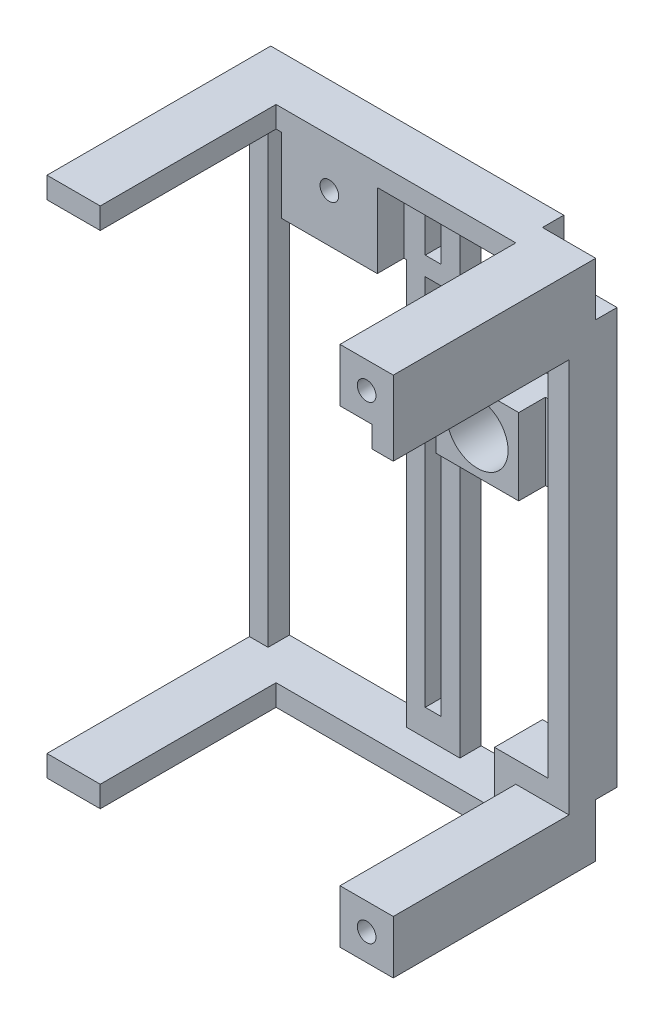
SolidWorks part; units mm, degrees
ref_plane "Front Plane" through (0, 0, 0) normal (0, 0, 1) x (1, 0, 0)
ref_plane "Top Plane" through (0, 0, 0) normal (0, 1, 0) x (1, 0, 0)
ref_plane "Right Plane" through (0, 0, 0) normal (1, 0, 0) x (0, 0, -1)
sketch "Sketch1" plane through (0, 0, 0) normal (0, 0, 1) x (1, 0, 0)
  line L0 (0, 94) -> (65, 94)
  line L1 (0, 0) -> (65, 0)
  line L2 (0, 0) -> (0, 98)
  line L3 (0, 98) -> (65, 98)
  line L4 (65, 0) -> (65, 98)
  line L5 (65, 98) -> (55, 98)
  line L6 (65, 98) -> (65, 88)
  line L7 (65, 88) -> (55, 88)
  line L8 (55, 98) -> (55, 88)
  line L9 (65, 0) -> (55, 0)
  line L10 (65, 0) -> (65, 10)
  line L11 (65, 10) -> (55, 10)
  line L12 (55, 0) -> (55, 10)
  line L13 (0, 4) -> (65, 4)
  line L14 (61, 0) -> (61, 98)
  line L15 (20, 9) -> (33, 9)
  line L16 (65, 98) -> (51, 98)
  line L17 (65, 98) -> (65, 84)
  line L18 (65, 84) -> (51, 84)
  line L19 (51, 98) -> (51, 84)
  line L20 (65, 0) -> (51, 0)
  line L21 (65, 0) -> (65, 14)
  line L22 (65, 14) -> (51, 14)
  line L23 (51, 0) -> (51, 14)
  line L24 (15, 84) -> (25, 84)
  line L25 (15, 84) -> (15, 94)
  line L26 (15, 94) -> (25, 94)
  line L27 (25, 84) -> (25, 94)
  line L28 (15, 84) -> (25, 94) construction
  line L29 (15, 94) -> (25, 84) construction
  line L30 (11, 94) -> (29, 94)
  line L31 (11, 94) -> (11, 80)
  line L32 (11, 80) -> (29, 80)
  line L33 (29, 94) -> (29, 80)
  line L34 (36, 70.6615) -> (39.5, 70.6615)
  line L35 (33, 9) -> (36, 9)
  line L36 (33, 9) -> (33, 79)
  line L37 (33, 79) -> (36, 79)
  line L38 (36, 9) -> (36, 79)
  line L40 (40.05, 70.6855) -> (55.55, 70.6855)
  line L41 (40.05, 70.6855) -> (40.05, 56.3145)
  line L42 (40.05, 56.3145) -> (55.55, 56.3145)
  line L43 (55.55, 70.6855) -> (55.55, 56.3145)
  line L44 (40.05, 70.6855) -> (55.55, 56.3145) construction
  line L45 (40.05, 56.3145) -> (55.55, 70.6855) construction
  circle A0 centre (20, 89) radius 1.75
  circle A1 centre (20, 9) radius 1.75
  circle A2 centre (47.8, 63.5) radius 5.75
  dimension "D9" = 3.5
  dimension "D11" = 3.5
  dimension "D28" = 11.5
  dimension "D1" = 98
  dimension "D2" = 65
  dimension "D3" = 10
  dimension "D4" = 10
  dimension "D5" = 10
  dimension "D6" = 10
  dimension "D7" = 45
  dimension "D8" = 9
  dimension "D10" = 80
  dimension "D12" = 4
  dimension "D13" = 4
  dimension "D14" = 4
  dimension "D15" = 14
  dimension "D16" = 14
  dimension "D17" = 14
  dimension "D18" = 14
  dimension "D19" = 10
  dimension "D20" = 9
  dimension "D21" = 9
  dimension "D22" = 4
  dimension "D23" = 13
  dimension "D24" = 70
  dimension "D25" = 3
  dimension "D26" = 3.5
  dimension "D27" = 13.2
  dimension "D29" = 20.5
  dimension "D30" = 15.5
extrude "Boss-Extrude2" add sketch "Sketch1" along normal blind 5 contours L33 L0 L27 L24 L25 L31 L32 | L19 L3 L2 L0 | L24 L27 L0 L25 A0 | L0 L19 L18 L14 L7 L8 | L3 L19 L0 L8 | L18 L4 L7 L14 | L22 L4 L18 L14 | L14 L7 L4 L0 | L7 L14 L0 L8 | L0 L14 L3 L8 | L14 L0 L4 L5 | L23 L13 L12 L11 L14 L22 | L13 L14 L11 L12 | L14 L13 L10 L11 | L4 L22 L14 L11 | L14 L9 L4 L13 | L1 L14 L13 L12 | L23 L1 L12 L13 | L1 L23 L13 L2 region at (25.5, 96, 0) region at (13, 93.772, 0) region at (25.5, 2, 0) region at (20, 93.8586, 0) region at (54.875, 10.125, 0) region at (53, 2, 0) region at (53, 96, 0) region at (58, 2, 0) region at (58, 7, 0) region at (58, 96, 0) region at (54.875, 87.875, 0) region at (63, 7, 0) region at (63, 2, 0) region at (63, 12, 0) region at (63, 49, 0) region at (63, 96, 0) region at (58, 91, 0) region at (63, 86, 0) region at (63, 91, 0)
extrude "Boss-Extrude4" add sketch "Sketch1<18>" against normal blind 4 contours L0 L33 L32 L31 L2 L13 L23 L22 L14 L18 L19 A1 | L1 L23 L13 L2 | L22 L4 L18 L14 | L0 L19 L18 L14 L7 L8 | L3 L19 L0 L8 | L18 L4 L7 L14 | L19 L3 L2 L0 | L33 L0 L27 L24 L25 L31 L32 | A1 | L23 L13 L12 L11 L14 L22 | L4 L22 L14 L11 | L23 L1 L12 L13 | L41 L40 L43 L42 region at (25.5, 96, 0) region at (28.9667, 46.5257, 0) region at (13, 93.772, 0) region at (25.5, 2, 0) region at (54.875, 10.125, 0) region at (53, 2, 0) region at (53, 96, 0) region at (54.875, 87.875, 0) region at (63, 12, 0) region at (63, 49, 0) region at (63, 86, 0) region at (18.2995, 9, 0)
sketch "Sketch1<18>" plane through (0, 0, 0) normal (0, 0, 1) x (1, 0, 0) same geometry as "Sketch1"
extrude "Boss-Extrude5" add sketch "Sketch1<22>" along normal blind 38 contours L1 L23 L13 L2 | L23 L1 L12 L13 | L1 L14 L13 L12 | L14 L9 L4 L13 | L14 L13 L10 L11 | L4 L22 L14 L11 | L22 L4 L18 L14 | L13 L14 L11 L12 | L18 L4 L7 L14 | L14 L7 L4 L0 | L7 L14 L0 L8 | L14 L0 L4 L5 | L0 L14 L3 L8 | L3 L19 L0 L8 | L19 L3 L2 L0 region at (25.5, 96, 0) region at (25.5, 2, 0) region at (53, 2, 0) region at (53, 96, 0) region at (58, 2, 0) region at (58, 7, 0) region at (58, 96, 0) region at (63, 7, 0) region at (63, 2, 0) region at (63, 12, 0) region at (63, 49, 0) region at (63, 96, 0) region at (58, 91, 0) region at (63, 86, 0) region at (63, 91, 0)
sketch "Sketch1<22>" plane through (0, 0, 0) normal (0, 0, 1) x (1, 0, 0) same geometry as "Sketch1"
sketch "Sketch2" plane through (0, 0, 38) normal (0, 0, 1) x (1, 0, 0)
  line L5 (0, 98) -> (65, 98) construction
  line L10 (65, 0) -> (65, 98) construction
  line L11 (0, 0) -> (65, 0) construction
  circle A0 centre (60, 93) radius 1.75
  circle A1 centre (60, 5) radius 1.75
  dimension "D1" = 3.5
  dimension "D2" = 5
  dimension "D4" = 3.5
  dimension "D3" = 5
  dimension "D5" = 5
  dimension "D6" = 5
extrude "Cut-Extrude1" cut sketch "Sketch2" against normal through all
extrude "Boss-Extrude6" add sketch "Sketch1<23>" along normal blind 5 contours L43 L40 L41 L42 A2
sketch "Sketch1<23>" plane through (0, 0, 0) normal (0, 0, 1) x (1, 0, 0) same geometry as "Sketch1"
extrude "Cut-Extrude4" cut sketch "Sketch1<25>" against normal through all contours A2 region at (47.8, 63.5, 0)
sketch "Sketch1<25>" plane through (0, 0, 0) normal (0, 0, 1) x (1, 0, 0) same geometry as "Sketch1"
sketch "Sketch9" plane through (0, 0, 38) normal (0, 0, 1) x (1, 0, 0)
  line L0 (10, 4) -> (10, 0)
  line L1 (0, 4) -> (51, 4) construction
  line L2 (0, 0) -> (65, 0) construction
  line L3 (0, 0) -> (0, 4) construction
  line L4 (10, 94) -> (10, 98)
  line L5 (0, 94) -> (11, 94) construction
  line L6 (0, 98) -> (65, 98) construction
  line L7 (0, 94) -> (0, 98) construction
  line L8 (65, 0) -> (65, 98) construction
  line L9 (51, 94) -> (10, 94)
  line L10 (51, 94) -> (51, 98)
  line L11 (51, 98) -> (10, 98)
  line L12 (10, 94) -> (10, 98)
  line L13 (51, 4) -> (10, 4)
  line L14 (51, 4) -> (51, 0)
  line L15 (51, 0) -> (10, 0)
  line L16 (10, 4) -> (10, 0)
  line L17 (61, 84) -> (65, 84)
  line L18 (61, 84) -> (61, 14)
  line L19 (61, 14) -> (65, 14)
  line L20 (65, 84) -> (65, 14)
  line L21 (61, 14) -> (51, 14) construction
  line L23 (55, 94) -> (51, 94)
  line L24 (55, 94) -> (55, 98)
  line L25 (55, 98) -> (51, 98)
  line L26 (51, 94) -> (51, 98)
  line L27 (65, 84) -> (61, 84)
  line L28 (65, 84) -> (65, 88)
  line L29 (65, 88) -> (61, 88)
  line L30 (61, 84) -> (61, 88)
  line L31 (65, 14) -> (61, 14)
  line L32 (65, 14) -> (65, 10)
  line L33 (65, 10) -> (61, 10)
  line L34 (61, 14) -> (61, 10)
  line L35 (55, 4) -> (51, 4)
  line L36 (55, 4) -> (55, 0)
  line L37 (55, 0) -> (51, 0)
  line L38 (51, 4) -> (51, 0)
  line M5 (65, 0) -> (65, 98)
  line M6 (65, 98) -> (0, 98)
  line M8 (0, 94) -> (55, 94)
  line M11 (61, 88) -> (61, 10)
  line M14 (55, 4) -> (0, 4)
  line M16 (0, 0) -> (65, 0)
  dimension "D1" = 10
  dimension "D2" = 10
  dimension "D3" = 0
extrude "Cut-Extrude6" cut sketch "Sketch9" against normal blind 33 contours L19 L17 M11 M5 | L10 L4 M8 M6 | L14 L0 M14 M16 | L36 L35 L38 L37 | L32 L31 L34 L33 | L24 L23 L26 L25 region at (30.5, 2, 38) region at (63, 49, 38) region at (30.5, 96, 38)
ref_plane "MirrorPlane" through (0, 98, 38) normal (0, 0, -1) x (-1, 0, 0)
sketch "Sketch10" plane through (0, 0, 0) normal (0, 0, 1) x (1, 0, 0)
  line L0 (0, 4) -> (51, 4) construction
  line L1 (0, 94) -> (3.5, 94)
  line L2 (0, 94) -> (0, 4)
  line L3 (0, 4) -> (3.5, 4)
  line L4 (3.5, 94) -> (3.5, 4)
  line L5 (29, 94) -> (51, 94) construction
  line L6 (33, 94) -> (29.5, 94)
  line L7 (33, 94) -> (33, 4)
  line L8 (33, 4) -> (29.5, 4)
  line L9 (29.5, 94) -> (29.5, 4)
  line L10 (61, 14) -> (61, 84) construction
  line L11 (61, 70.6855) -> (39.5, 70.6855)
  line L12 (61, 70.6855) -> (61, 94)
  line L13 (61, 94) -> (39.5, 94)
  line L14 (39.5, 70.6855) -> (39.5, 94)
  line L15 (29, 94) -> (51, 94) construction
  line L16 (36, 9) -> (36, 79) construction
  line L17 (51, 94) -> (51, 84)
  line L18 (36, 79) -> (33, 79)
  line L19 (36, 79) -> (36, 82.5)
  line L20 (36, 82.5) -> (33, 82.5)
  line L21 (33, 79) -> (33, 82.5)
  line L22 (39.5, 56.3145) -> (61, 56.3145)
  line L23 (39.5, 56.3145) -> (39.5, 4)
  line L24 (39.5, 4) -> (61, 4)
  line L25 (61, 56.3145) -> (61, 4)
  line L27 (61, 4) -> (51, 4)
  line L28 (36, 82.5) -> (36, 94)
  line L29 (29.5, 94) -> (29, 94)
  line L30 (61, 4) -> (61, 14)
  line L31 (61, 14) -> (51, 14)
  line L32 (51, 4) -> (51, 14)
  line L33 (29.5, 94) -> (29.5, 80)
  line L34 (29.5, 80) -> (29, 80)
  line L35 (29, 94) -> (29, 80)
  line M17 (55.55, 56.3145) -> (40.05, 56.3145)
  line M19 (40.05, 70.6855) -> (55.55, 70.6855)
  line M24 (11, 94) -> (0, 94)
  line M26 (0, 4) -> (51, 4)
  line M27 (51, 4) -> (51, 14)
  line M28 (51, 14) -> (61, 14)
  line M29 (61, 14) -> (61, 84)
  line M30 (61, 84) -> (51, 84)
  line M31 (51, 84) -> (51, 94)
  line M32 (51, 94) -> (29, 94)
  line M34 (29, 80) -> (11, 80)
  line M35 (11, 80) -> (11, 94)
  dimension "D1" = 3.5
  dimension "D2" = 3.5
  dimension "D3" = 3.5
  dimension "D4" = 3.5
  dimension "D5" = 3
extrude "Cut-Extrude7" cut sketch "Sketch10" against normal through all contours L20 L28 L7 M32 | L14 L11 M19 M29 M30 M31 M32 | L9 L4 M34 M35 M24 M26 | L22 L23 M26 M27 M28 M29 M17 region at (16.0333, 44.2705, 0) region at (49.6889, 32.2218, 0) region at (34.5, 88.25, 0) region at (48.817, 80.6837, 0)
